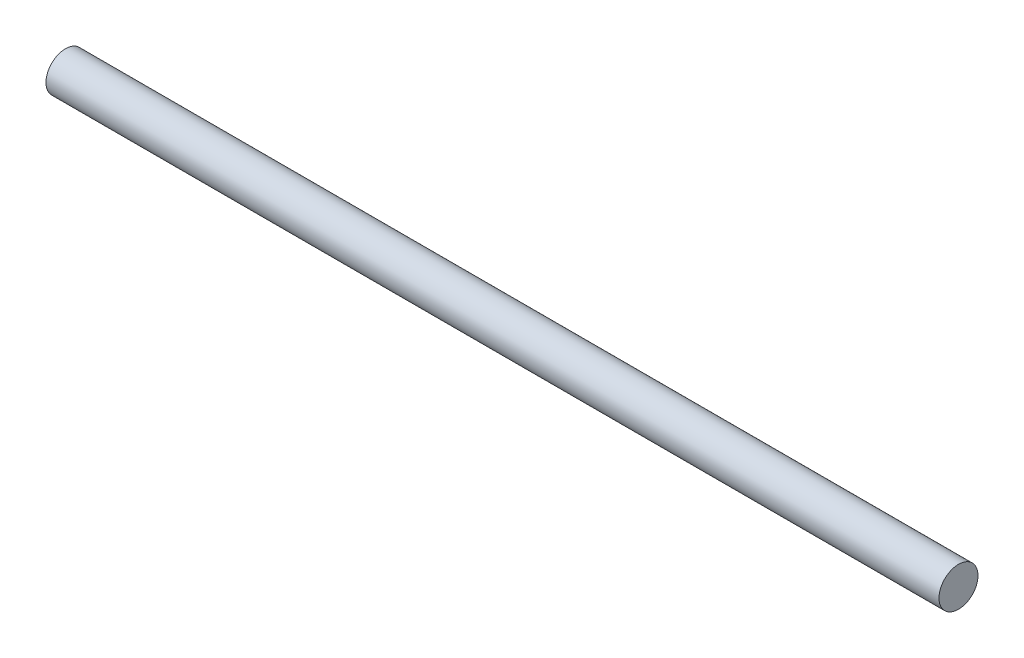
SolidWorks part; units mm, degrees
material "Copper"
ref_plane "Front Plane" through (0, 0, 0) normal (0, 0, 1) x (1, 0, 0)
ref_plane "Top Plane" through (0, 0, 0) normal (0, 1, 0) x (1, 0, 0)
ref_plane "Right Plane" through (0, 0, 0) normal (1, 0, 0) x (0, 0, -1)
sketch "Sketch1" plane through (0, 0, 0) normal (1, 0, 0) x (0, 0, -1)
  circle A0 centre (0, 0) radius 0.2921
  dimension "D1" = 0.5842
extrude "Boss-Extrude1" add sketch "Sketch1" along normal blind 13.37
